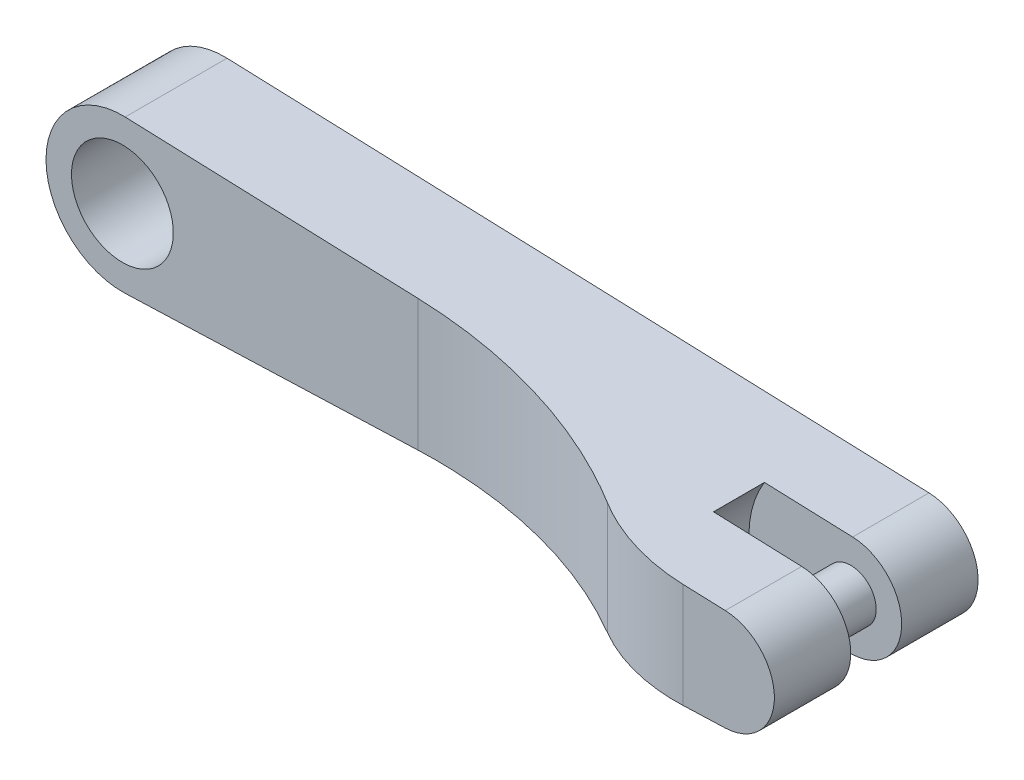
SolidWorks part; units mm, degrees
ref_plane "Front Plane" through (0, 0, 0) normal (0, 0, 1) x (1, 0, 0)
ref_plane "Top Plane" through (0, 0, 0) normal (0, 1, 0) x (1, 0, 0)
ref_plane "Right Plane" through (0, 0, 0) normal (1, 0, 0) x (0, 0, -1)
sketch "Sketch2" plane through (0, 0, 0) normal (0, 0, 1) x (1, 0, 0)
  line L0 (-373.4674, 0) -> (398.5836, 0) construction
  line L1 (-287.2826, 74.9508) -> (401.8116, 49.9672)
  line L2 (-287.2826, -74.9508) -> (401.8116, -49.9672)
  circle A0 centre (-290, 0) radius 50
  arc A1 (-287.2826, 74.9508) -> (-287.2826, -74.9508) centre (-290, 0) ccw
  circle A2 centre (400, 0) radius 25 construction
  circle A3 centre (400, 0) radius 50 construction
  arc A4 (401.8116, -49.9672) -> (401.8116, 49.9672) centre (400, 0) ccw
  dimension "D1" = 100
  dimension "D3" = 150
  dimension "D4" = 50
  dimension "D5" = 100
  dimension "D2" = 290
  dimension "D6" = 400
extrude "Boss-Extrude1" add sketch "Sketch2" along normal mid plane 100
sketch "Sketch6" plane through (0, 0, 50) normal (0, 0, 1) x (1, 0, 0)
  line L2 (-287.2826, -74.9508) -> (401.8116, -49.9672)
  line L3 (401.8116, 49.9672) -> (-287.2826, 74.9508)
  line L4 (-287.2826, -74.9508) -> (401.8116, -49.9672)
  line L5 (401.8116, 49.9672) -> (-287.2826, 74.9508)
  circle A0 centre (-290, 0) radius 50 construction
  circle A1 centre (-290, 0) radius 50
  arc A2 (-287.2826, 74.9508) -> (-287.2826, -74.9508) centre (-290, 0) ccw
  arc A3 (401.8116, -49.9672) -> (401.8116, 49.9672) centre (400, 0) ccw
  arc A4 (-287.2826, 74.9508) -> (-287.2826, -74.9508) centre (-290, 0) ccw
  arc A5 (401.8116, -49.9672) -> (401.8116, 49.9672) centre (400, 0) ccw
  dimension "D1" = 0
extrude "Boss-Extrude4" add sketch "Sketch6" along normal blind 100
sketch "Sketch8" plane through (0, 0, 0) normal (0, 0, 1) x (1, 0, 0)
  circle A0 centre (400, 0) radius 100
  circle A1 centre (400, 0) radius 25
  dimension "D1" = 50
  dimension "D2" = 200
extrude "Cut-Extrude1" cut sketch "Sketch8" along normal blind 25 and the other way blind 25 from offset 50
sketch "Sketch9" plane through (0, 0, 0) normal (0, 1, 0) x (1, 0, 0)
  line L0 (-365, -50) -> (315.2659, -50) construction
  line L1 (-365, 50) -> (-365, -150) construction
  line L2 (315.2659, -75) -> (315.2659, -25) construction
  line L3 (-365, -50) -> (0, -50)
  line L4 (401.8116, -150) -> (-287.2826, -150) construction
  line L5 (-365, -50) -> (-365, -150)
  line L6 (-365, -150) -> (300, -150)
  arc A0 (0, -50) -> (300, -150) centre (0, -550) cw
  dimension "D1" = 500
extrude "Cut-Extrude2" cut sketch "Sketch9" against normal up to next and the other way up to next contours L6 A0 L3 L5
fillet "Fillet1" radius 200 1 edges at (300, 0, 150)
